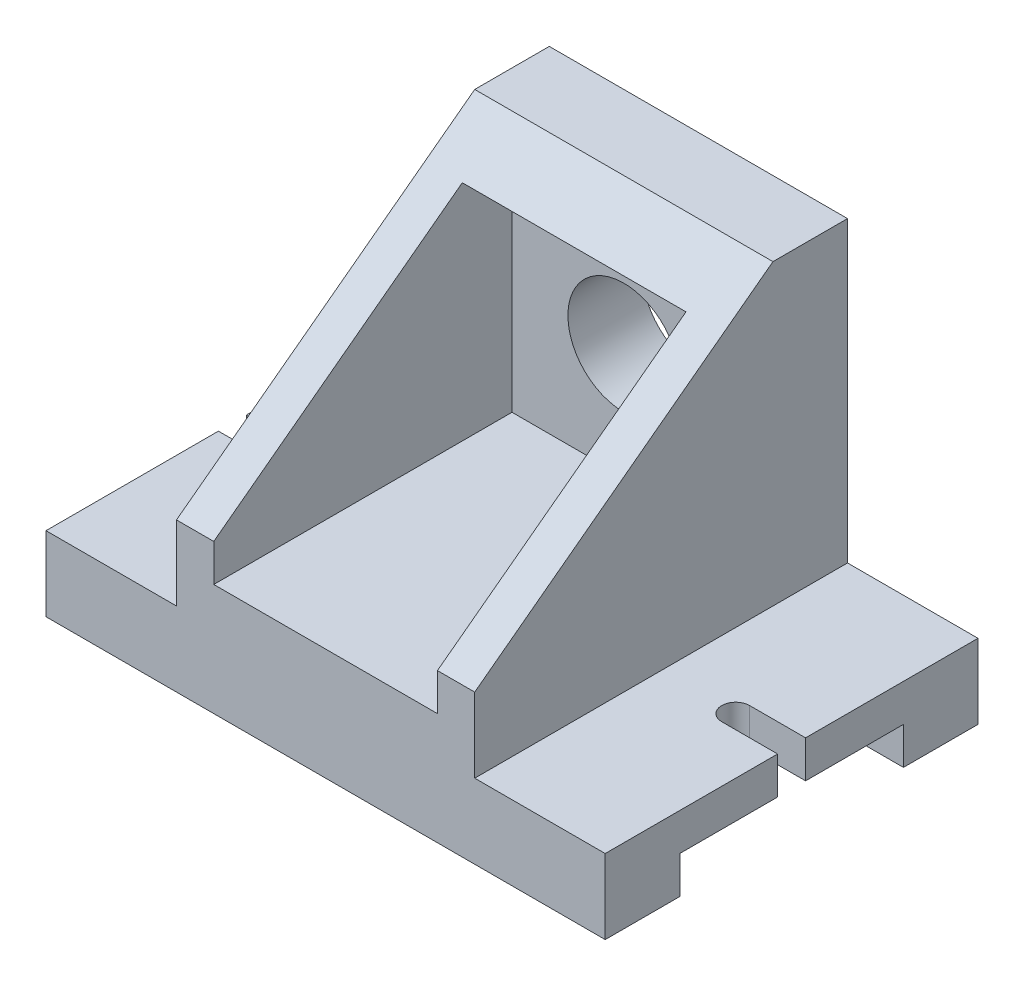
SolidWorks part; units mm, degrees
ref_plane "Front Plane" through (0, 0, 0) normal (0, 0, 1) x (1, 0, 0)
ref_plane "Top Plane" through (0, 0, 0) normal (0, 1, 0) x (1, 0, 0)
ref_plane "Right Plane" through (0, 0, 0) normal (1, 0, 0) x (0, 0, -1)
sketch "Sketch1" plane through (0, 0, 0) normal (1, 0, 0) x (0, 0, -1)
  line L1 (-50, 50) -> (50, 50)
  line L2 (-50, 50) -> (-50, -50)
  line L3 (-50, -50) -> (50, -50)
  line L4 (50, 50) -> (50, -50)
  line L5 (-50, 50) -> (50, -50) construction
  line L6 (-50, -50) -> (50, 50) construction
  point P0 (0, 0)
  dimension "D1" = 100
  dimension "D2" = 100
extrude "Boss-Extrude1" add sketch "Sketch1" along normal blind 75 and the other way blind 75
sketch "Sketch2" plane through (0, 50, 0) normal (0, 1, 0) x (1, 0, 0)
  line L0 (-75, 50) -> (75, 50) construction
  line L1 (40, 50) -> (75, 50)
  line L2 (40, 50) -> (40, -50)
  line L3 (40, -50) -> (75, -50)
  line L4 (75, 50) -> (75, -50)
  line L5 (-75, -50) -> (75, -50) construction
  line L6 (75, 50) -> (75, -50) construction
  line L7 (0, -55) -> (0, 55) construction
  line L8 (-75, 50) -> (-75, -50)
  line L9 (-40, -50) -> (-75, -50)
  line L10 (-40, 50) -> (-40, -50)
  line L11 (-40, 50) -> (-75, 50)
  dimension "D1" = 40
extrude "Cut-Extrude1" cut sketch "Sketch2" against normal blind 80
sketch "Sketch3" plane through (40, 0, 0) normal (1, 0, 0) x (0, 0, -1)
  line L0 (30, 50) -> (-50, -10)
  line L1 (50, 50) -> (-50, 50) construction
  line L2 (-50, -30) -> (-50, 50) construction
  line L3 (-50, -10) -> (-50, 50)
  line L4 (30, 50) -> (-50, 50)
  line L5 (-50, -50) -> (50, -50) construction
  dimension "D1" = 20
  dimension "D2" = 40
extrude "Cut-Extrude2" cut sketch "Sketch3" against normal through all
sketch "Sketch5" plane through (0, 0, 50) normal (0, 0, 1) x (1, 0, 0)
  line L15 (0, 0) -> (0, 58.267) construction
  line L16 (-30, 40) -> (30, 40)
  line L17 (-30, 40) -> (-30, -20)
  line L18 (-30, -20) -> (30, -20)
  line L19 (30, 40) -> (30, -20)
  line L20 (-40, 50) -> (40, 50) construction
  dimension "D1" = 60
  dimension "D2" = 60
  dimension "D3" = 10
extrude "Cut-Extrude3" cut sketch "Sketch5" against normal blind 80
sketch "Sketch6" plane through (75, 0, 0) normal (1, 0, 0) x (0, 0, -1)
  line L0 (-50, -50) -> (50, -50) construction
  line L1 (-30, -40) -> (30, -40)
  line L2 (-30, -40) -> (-30, -50)
  line L3 (-30, -50) -> (30, -50)
  line L4 (30, -40) -> (30, -50)
  line L5 (50, -50) -> (50, -30) construction
  line L6 (50, -30) -> (-50, -30) construction
  dimension "D1" = 60
  dimension "D2" = 20
  dimension "D3" = 10
extrude "Cut-Extrude5" cut sketch "Sketch6" against normal through all
sketch "Sketch7" plane through (0, -30, 0) normal (0, 1, 0) x (1, 0, 0)
  line L0 (60, 3.75) -> (75, 3.75)
  line L1 (75, -50) -> (75, 50) construction
  line L2 (60, -3.75) -> (75, -3.75)
  line L3 (0, 0) -> (98.2364, 0) construction
  line L4 (75, -3.75) -> (75, 3.75)
  arc A0 (60, -3.75) -> (60, 3.75) centre (60, 0) cw
  point P3 (81.5272, 0)
  point P11 (59.7429, 10.5331)
  dimension "D2" = 3.75
  dimension "D1" = 7.5
  dimension "D3" = 15
extrude "Cut-Extrude6" cut sketch "Sketch7" against normal through all
mirror "Mirror1" about plane through (0, 0, 0) normal (1, 0, 0) of "Cut-Extrude6"
hole_wizard "Hole1" positions "Sketch8" profile "Sketch9" legacy end condition through all
sketch "Sketch8" plane through (0, 0, -30) normal (0, 0, 1) x (1, 0, 0)
  line L0 (-40, 50) -> (40, 50) construction
  point P0 (0, 10)
  dimension "D1" = 40
sketch "Sketch9" plane through (0, 10, -30) normal (1, 0, 0) x (0, -1, 0)
  line L0 (0, 0) -> (0, 20)
  line L1 (0, 20) -> (15, 20)
  line L2 (15, 20) -> (15, 0)
  line L3 (15, 0) -> (0, 0)
  line L4 (0, 110) -> (0, -10) construction
  dimension "Diameter" = 30
  dimension "Depth" = 20
